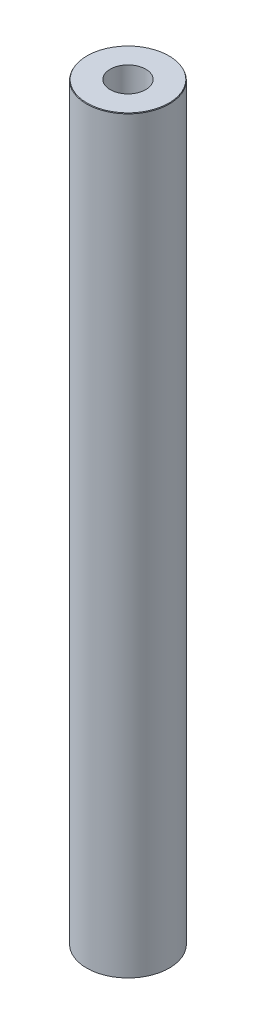
SolidWorks part; units mm, degrees
ref_plane "Front Plane" through (0, 0, 0) normal (0, 0, 1) x (1, 0, 0)
ref_plane "Top Plane" through (0, 0, 0) normal (0, 1, 0) x (1, 0, 0)
ref_plane "Right Plane" through (0, 0, 0) normal (1, 0, 0) x (0, 0, -1)
sketch "Sketch1" plane through (0, 0, 0) normal (0, 1, 0) x (1, 0, 0)
  circle A0 centre (0, 0) radius 25
  dimension "SHAFT_OD" = 50
extrude "Boss-Extrude1" add sketch "Sketch1" along normal blind 453.3695
sketch "Sketch2" plane through (0, 0, 0) normal (0, 1, 0) x (1, 0, 0)
  circle A0 centre (0, 0) radius 10.762
  dimension "BORE_D" = 21.524
extrude "Cut-Extrude1" cut sketch "Sketch2" along normal through all
chamfer "Chamfer1" distance 0.401 angle 30 2 edges at (0, 453.3695, 25) (0, 0, 25) first distance on face at (0, 453.3695, 25) first distance on face at (0, 0, 10.762)
